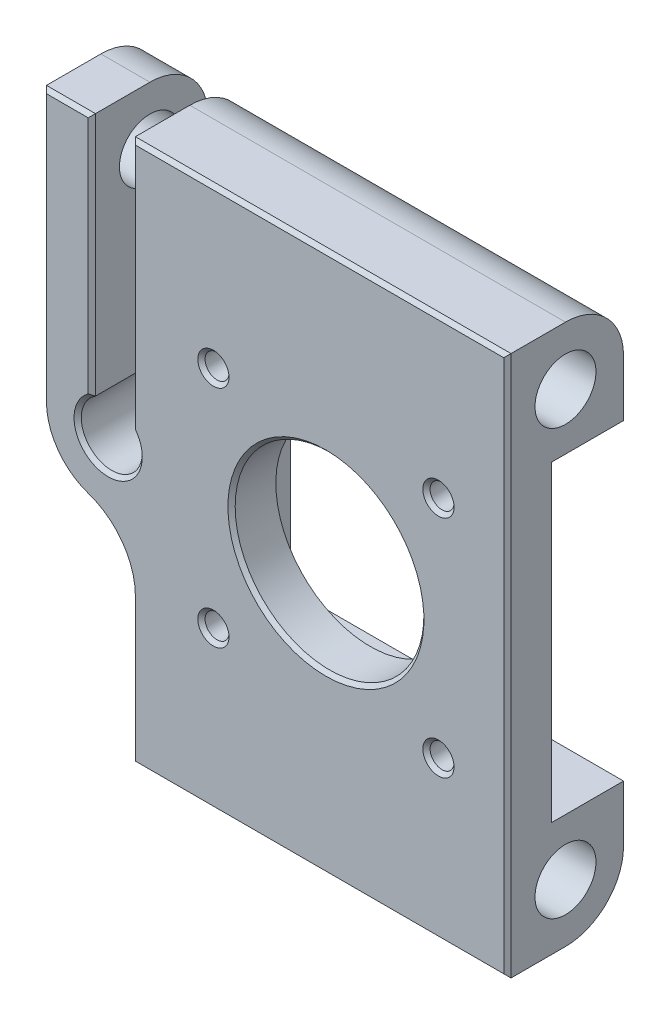
SolidWorks part; units mm, degrees
material "ABS"
ref_plane "Front Plane" through (0, 0, 0) normal (0, 0, 1) x (1, 0, 0)
ref_plane "Top Plane" through (0, 0, 0) normal (0, 1, 0) x (1, 0, 0)
ref_plane "Right Plane" through (0, 0, 0) normal (1, 0, 0) x (0, 0, -1)
sketch "Sketch2" plane through (0, 0, 0) normal (1, 0, 0) x (0, 0, -1)
  line L10 (-75.6076, 29.5315) -> (-75.6076, 37.2815)
  line L11 (-75.6076, 37.2815) -> (-85.5076, 37.2815)
  line L12 (-85.5076, 37.2815) -> (-85.5076, 80.2815)
  line L13 (-85.5076, 80.2815) -> (-75.6076, 80.2815)
  line L14 (-75.6076, 80.2815) -> (-75.6076, 88.0315)
  line L25 (-83.6076, 96.0315) -> (-91.6076, 96.0315)
  line L26 (-91.6076, 96.0315) -> (-91.6076, 21.5315)
  line L27 (-91.6076, 21.5315) -> (-83.6076, 21.5315)
  arc A0 (-75.6076, 29.5315) -> (-83.6076, 21.5315) centre (-83.6076, 29.5315) cw
  arc A1 (-83.6076, 96.0315) -> (-75.6076, 88.0315) centre (-83.6076, 88.0315) cw
  dimension "D2" = 8
  dimension "D3" = 8
  dimension "D1" = 74.5
  dimension "D4" = 16
  dimension "D5" = 16
  dimension "D6" = 43
  dimension "D7" = 9.9
  dimension "D8" = 43
  dimension "D9" = 8
  dimension "D10" = 15.75
extrude "Boss-Extrude1" add sketch "Sketch2" along normal blind 45.9
sketch "Sketch3" plane through (0, 0, 0) normal (-1, 0, 0) x (0, 0, 1)
  line L0 (75.6076, 37.2815) -> (75.6076, 80.2815)
  line L1 (91.6076, 21.5315) -> (91.6076, 96.0315)
  line L8 (83.6076, 21.5315) -> (91.6076, 21.5315)
  line L9 (91.6076, 21.5315) -> (91.6076, 96.0315)
  line L10 (91.6076, 96.0315) -> (83.6076, 96.0315)
  line L11 (75.6076, 88.0315) -> (75.6076, 80.2815)
  line L12 (75.6076, 80.2815) -> (85.5076, 80.2815)
  line L13 (85.5076, 80.2815) -> (85.5076, 37.2815)
  line L14 (85.5076, 37.2815) -> (75.6076, 37.2815)
  line L15 (75.6076, 37.2815) -> (75.6076, 29.5315)
  line L16 (83.6076, 21.5315) -> (91.6076, 21.5315)
  line L18 (91.6076, 96.0315) -> (83.6076, 96.0315)
  line L19 (75.6076, 88.0315) -> (75.6076, 80.2815)
  line L23 (75.6076, 37.2815) -> (75.6076, 29.5315)
  arc A2 (75.6076, 29.5315) -> (83.6076, 21.5315) centre (83.6076, 29.5315) ccw
  arc A3 (83.6076, 96.0315) -> (75.6076, 88.0315) centre (83.6076, 88.0315) ccw
  arc A4 (75.6076, 29.5315) -> (83.6076, 21.5315) centre (83.6076, 29.5315) ccw
  arc A5 (83.6076, 96.0315) -> (75.6076, 88.0315) centre (83.6076, 88.0315) ccw
  dimension "D1" = 0
extrude "Boss-Extrude2" add sketch "Sketch3" along normal blind 5.85
sketch "Sketch5" plane through (0, 0, 85.5076) normal (0, 0, -1) x (-1, 0, 0)
  line L0 (-45.9, 37.2815) -> (-45.9, 80.2815) construction
  line L1 (-45.9, 21.5315) -> (5.85, 21.5315) construction
  line L2 (-20.9, 58.7815) -> (-45.9, 58.7815) construction
  circle A0 centre (-20.9, 58.7815) radius 13
  dimension "D1" = 25
  dimension "D2" = 26
  dimension "D3" = 37.25
extrude "Cut-Extrude1" cut sketch "Sketch5" against normal through all
sketch "Sketch7" plane through (0, 0, 75.6076) normal (0, 0, -1) x (-1, 0, 0)
  line L0 (18.1, 58.7815) -> (18.1, 96.0315)
  line L1 (5.85, 96.0315) -> (18.1, 96.0315)
  line L2 (5.85, 88.0315) -> (5.85, 50.3888)
  line L4 (9.1, 58.7815) -> (9.1, 96.0315) construction
  line L5 (9.1, 96.0315) -> (11.35, 96.0315)
  line L6 (11.35, 96.0315) -> (11.35, 62.328)
  line L7 (6.85, 96.0315) -> (6.85, 62.328)
  line L8 (-45.9, 96.0315) -> (5.85, 96.0315) construction
  line L9 (5.85, 88.0315) -> (5.85, 29.5315) construction
  arc A0 (6.85, 62.328) -> (11.35, 62.328) centre (9.1, 58.7815) ccw
  circle A1 centre (-20.9, 58.7815) radius 13 construction
  arc A2 (5.85, 50.3888) -> (18.1, 58.7815) centre (9.1, 58.7815) ccw
  dimension "D1" = 8.4
  dimension "D2" = 30
  dimension "D3" = 18
  dimension "D4" = 2.25
  dimension "D5" = 2.25
  dimension "D6" = 37.25
extrude "Boss-Extrude3" add sketch "Sketch7" against normal up to surface (16 mm away) contours L2 A2 L0 L1 L6 A0 region at (-14.184, 72.7043, 75.6076) up to face at (20.9, 71.7815, 91.6076)
extrude "Cut-Extrude3" cut sketch "Sketch7<3>" against normal through all contours L2 A0 region at (-5.4661, 58.7815, 75.6076)
sketch "Sketch7<3>" plane through (0, 0, 75.6076) normal (0, 0, -1) x (-1, 0, 0) same geometry as "Sketch7"
fillet "Fillet2" radius 9 1 edges at (-5.85, 50.3888, 83.6076)
sketch "Sketch6" plane through (45.9, 0, 0) normal (1, 0, 0) x (0, 0, -1)
  line L0 (-75.6076, 80.2815) -> (-75.6076, 88.0315) construction
  line L1 (-83.6076, 96.0315) -> (-91.6076, 96.0315) construction
  line L2 (-91.6076, 96.0315) -> (-91.6076, 21.5315) construction
  line L3 (-91.6076, 21.5315) -> (-83.6076, 21.5315) construction
  circle A0 centre (-83.6076, 88.0315) radius 4.2
  circle A1 centre (-83.6076, 29.5315) radius 4.2
  dimension "D1" = 8.4
  dimension "D2" = 8
  dimension "D3" = 8
  dimension "D4" = 8
  dimension "D5" = 8
extrude "Cut-Extrude2" cut sketch "Sketch6" against normal through all
sketch "Sketch9" plane through (0, 0, 85.5076) normal (0, 0, -1) x (-1, 0, 0)
  line L1 (-5.4, 43.2815) -> (-36.4, 43.2815) construction
  line L2 (-5.4, 43.2815) -> (-5.4, 74.2815) construction
  line L3 (-5.4, 74.2815) -> (-36.4, 74.2815) construction
  line L4 (-36.4, 43.2815) -> (-36.4, 74.2815) construction
  line L5 (-5.4, 43.2815) -> (-36.4, 74.2815) construction
  line L6 (-5.4, 74.2815) -> (-36.4, 43.2815) construction
  circle A0 centre (-36.4, 74.2815) radius 1.65
  point P0 (-20.9, 58.7815)
  dimension "D3" = 3.3
  dimension "D1" = 31
  dimension "D2" = 31
extrude "Cut-Extrude5" cut sketch "Sketch9" against normal through all
pattern_circular "CirPattern1" count 4 over 360 about axis through (20.9, 58.7815, 85.5076) along (0, 0, -1) of "Cut-Extrude5"
sketch "Sketch10" plane through (-11.35, 0, 0) normal (1, 0, 0) x (0, 0, -1)
  line L2 (-75.6076, 62.328) -> (-75.6076, 96.0315) construction
  line L3 (-75.6076, 96.0315) -> (-91.6076, 96.0315) construction
  line L8 (-75.6076, 80.2815) -> (-75.6076, 88.0315) construction
  line L14 (-75.6076, 80.2815) -> (-75.6076, 96.0315)
  line L15 (-75.6076, 96.0315) -> (-83.6076, 96.0315)
  line L20 (-75.6076, 80.2815) -> (-75.6076, 88.0315)
  arc A1 (-75.6076, 88.0315) -> (-83.6076, 96.0315) centre (-83.6076, 88.0315) ccw construction
  arc A3 (-75.6076, 88.0315) -> (-83.6076, 96.0315) centre (-83.6076, 88.0315) ccw
  line M5 (-75.6076, 96.0315) -> (-91.6076, 96.0315)
extrude "Cut-Extrude6" cut sketch "Sketch10" against normal through all contours A3 L14 M5 region at (-11.35, 94.2445, 77.3945)
chamfer "Chamfer1" distance 0.5 angle 45 16 edges at (36.4, 75.9315, 91.6076) (38.05, 43.2815, 91.6076) (20.9, 71.7815, 91.6076) (5.4, 41.6315, 91.6076) (3.75, 74.2815, 91.6076) (-9.7681, 54.6349, 91.6076) (-5.85, 78.7367, 91.6076) (20.025, 96.0315, 91.6076) (45.9, 58.7815, 91.6076) (20.025, 21.5315, 91.6076) (-5.85, 31.628, 91.6076) (-7.5399, 46.9746, 91.6076) (-16.4101, 53.5315, 91.6076) (-18.1, 77.4065, 91.6076) (-14.725, 96.0315, 91.6076) (-11.35, 79.1797, 91.6076)
